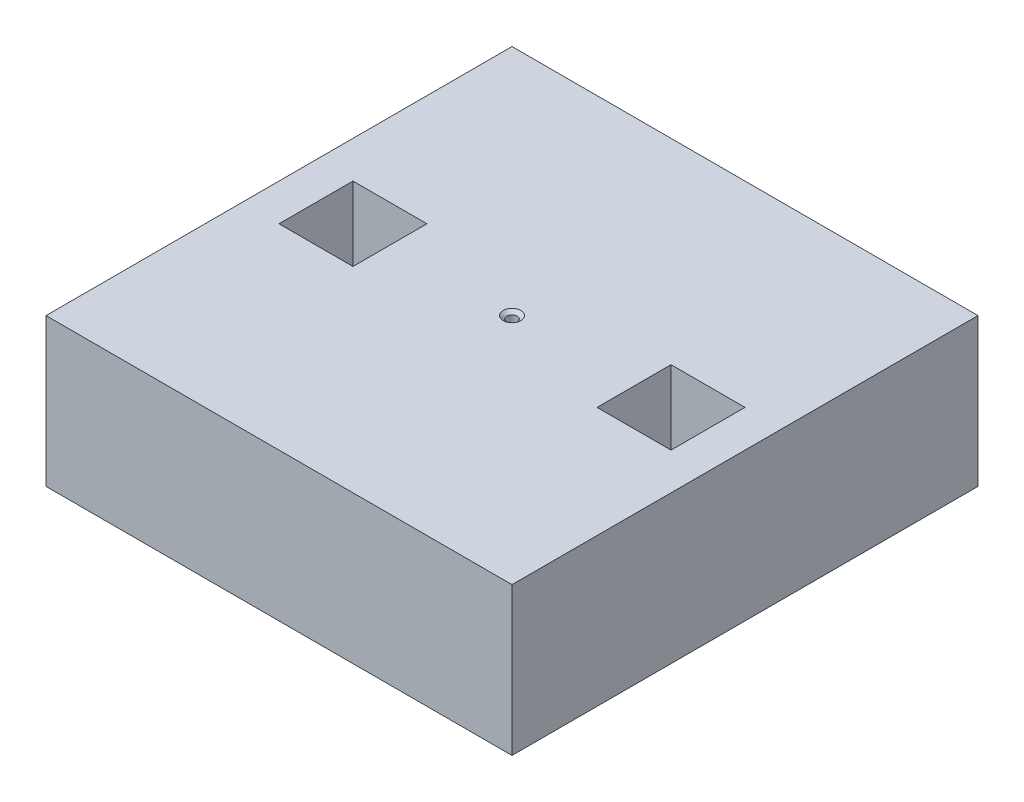
SolidWorks part; units mm, degrees
ref_plane "Front Plane" through (0, 0, 0) normal (0, 0, 1) x (1, 0, 0)
ref_plane "Top Plane" through (0, 0, 0) normal (0, 1, 0) x (1, 0, 0)
ref_plane "Right Plane" through (0, 0, 0) normal (1, 0, 0) x (0, 0, -1)
sketch "Sketch1" plane through (0, 0, 0) normal (0, 1, 0) x (1, 0, 0)
  line L0 (-40, 0) -> (40, 0) construction
  line L1 (-40, 40) -> (40, 40)
  line L2 (-40, 40) -> (-40, -40)
  line L3 (-40, -40) -> (40, -40)
  line L4 (40, 40) -> (40, -40)
  line L5 (-40, 40) -> (40, -40) construction
  line L6 (-40, -40) -> (40, 40) construction
  line L7 (-33.65, -6.35) -> (-20.95, -6.35)
  line L8 (-33.65, -6.35) -> (-33.65, 6.35)
  line L9 (-33.65, 6.35) -> (-20.95, 6.35)
  line L10 (-20.95, -6.35) -> (-20.95, 6.35)
  line L11 (-33.65, -6.35) -> (-20.95, 6.35) construction
  line L12 (-33.65, 6.35) -> (-20.95, -6.35) construction
  line L13 (20.95, 6.35) -> (33.65, 6.35)
  line L14 (20.95, 6.35) -> (20.95, -6.35)
  line L15 (20.95, -6.35) -> (33.65, -6.35)
  line L16 (33.65, 6.35) -> (33.65, -6.35)
  line L17 (20.95, 6.35) -> (33.65, -6.35) construction
  line L18 (20.95, -6.35) -> (33.65, 6.35) construction
  line L19 (0, 40) -> (0, -40) construction
  point P0 (0, 0)
  point P6 (-27.3, 0)
  point P11 (27.3, 0)
  point P18 (0, 0)
  point P19 (0, 0)
  point P22 (0, 0)
  point P23 (0, 0)
  dimension "D1" = 80
  dimension "D2" = 80
  dimension "D3" = 6.35
  dimension "D4" = 6.35
  dimension "D5" = 12.7
  dimension "D6" = 12.7
  dimension "D7" = 12.7
  dimension "D8" = 12.7
extrude "Boss-Extrude1" add sketch "Sketch1" along normal blind 25.4
hole_wizard "CSK for #0 Flat Head Machine Screw (100)1" positions "Sketch2" profile "Sketch3" countersink size "#0" standard "ANSI Inch" end condition through all
sketch "Sketch2" plane through (0, 25.4, 0) normal (0, 1, 0) x (1, 0, 0)
  point P0 (0, 0)
sketch "Sketch3" plane through (0, 25.4, 0) normal (1, 0, 0) x (0, 0, 1)
  line L0 (0, 0) -> (0, 25.4)
  line L1 (0, 25.4) -> (0.889, 25.4)
  line L2 (0.889, 25.4) -> (0.889, 0.5222)
  line L3 (0.889, 0.5222) -> (1.5113, 0)
  line L5 (1.5113, 0) -> (0, 0)
  line L6 (-0.889, 0.5222) -> (-1.5113, 0) construction
  line L11 (0, -6.35) -> (0, 107.95) construction
  dimension "Thru Hole Dia." = 1.778
  dimension "Thru Hole Depth" = 25.4
  dimension "Near C'Sink Dia." = 3.0226
  dimension "Near C'Sink Angle" = 100
